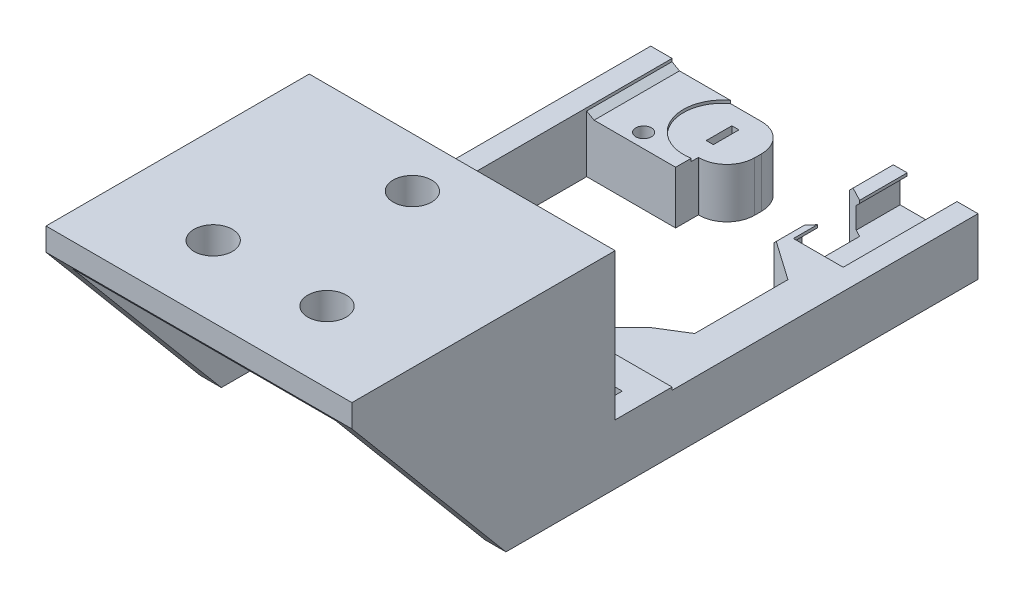
SolidWorks part; units mm, degrees
ref_plane "Front Plane" through (0, 0, 0) normal (0, 0, 1) x (1, 0, 0)
ref_plane "Top Plane" through (0, 0, 0) normal (0, 1, 0) x (1, 0, 0)
ref_plane "Right Plane" through (0, 0, 0) normal (1, 0, 0) x (0, 0, -1)
sketch "Sketch1" plane through (0, 0, 0) normal (0, 1, 0) x (1, 0, 0)
  line L0 (0, 0) -> (0, 59.6401) construction
  line L1 (-18.5, -19.2885) -> (-21.5, -19.2885)
  line L2 (18.5, 17.7115) -> (21.5, 17.7115)
  line L3 (18.5, 17.7115) -> (18.5, 65.7115)
  line L4 (18.5, 65.7115) -> (21.5, 65.7115)
  line L5 (21.5, 17.7115) -> (21.5, 65.7115)
  line L6 (18.5, 17.7115) -> (21.5, 17.7115)
  line L7 (18.5, 17.7115) -> (18.5, -19.2885)
  line L8 (18.5, -19.2885) -> (21.5, -19.2885)
  line L9 (21.5, 17.7115) -> (21.5, -19.2885)
  line L10 (-21.5, 17.7115) -> (-21.5, -19.2885)
  line L11 (-18.5, 17.7115) -> (-21.5, 17.7115)
  line L12 (-18.5, 17.7115) -> (-18.5, -19.2885)
  line L13 (-18.5, 65.7115) -> (-21.5, 65.7115)
  line L14 (-21.5, 17.7115) -> (-21.5, 65.7115)
  line L15 (-18.5, 17.7115) -> (-21.5, 17.7115)
  line L16 (-18.5, 17.7115) -> (-18.5, 65.7115)
  dimension "18" = 18.5
  dimension "D2" = 3
  dimension "D3" = 37
  dimension "D4" = 48
extrude "Boss-Extrude1" add sketch "Sketch1" against normal blind 8 contours L12 L11 L10 L1 | L11 L16 L13 L14 | L9 L2 L7 L8 | L2 L5 L4 L3 region at (-20, 0, 0.7885) region at (-20, 0, -41.7115) region at (20, 0, -41.7115) region at (20, 0, 0.7885)
sketch "Sketch2" plane through (21.5, 0, 0) normal (1, 0, 0) x (0, 0, -1)
  line L0 (-19.2885, -4) -> (65.7115, -4) construction
  line L1 (-19.2885, -8) -> (-19.2885, 0) construction
  line L2 (65.7115, -8) -> (65.7115, 0) construction
  line L3 (65.7115, -8) -> (-19.2885, -8) construction
  line L4 (17.7115, 0) -> (17.7115, -8) construction
  line L5 (65.7115, 0) -> (-19.2885, 0) construction
  circle A0 centre (11.7115, -4) radius 1.5
  circle A2 centre (-8.2885, -4) radius 1.5
  circle A3 centre (1.7115, -4) radius 1.5 [skipped]
  dimension "D2" = 3
  dimension "D1" = 4
  dimension "D3" = 37
  dimension "D4" = 6
  dimension "D5" = 3
extrude "Cut-Extrude1" [suppressed] cut sketch "Sketch2" against normal through all both and the other way through all
chamfer "Chamfer1" [suppressed] distance 1 angle 48
chamfer "Chamfer2" [suppressed] distance 1 angle 48
sketch "Sketch4" plane through (0, -8, 0) normal (0, -1, 0) x (1, 0, 0)
  line L0 (-21.5, -65.7115) -> (-21.5, 19.2885) construction
  line L1 (-2, -65.7115) -> (-21.5, -65.7115)
  line L2 (-2, -65.7115) -> (-2, -56.9115)
  line L3 (-2, -56.9115) -> (-21.5, -56.9115)
  line L4 (-21.5, -65.7115) -> (-21.5, -56.9115)
  line L10 (-18.5, -65.7115) -> (-18.5, 19.2885) construction
  line L13 (-18.5, -65.7115) -> (-21.5, -65.7115) construction
  dimension "D1" = 8.8
  dimension "D2" = 16.5
extrude "Boss-Extrude3" add sketch "Sketch4" against normal blind 6.6
sketch "Sketch3" plane through (0, -8, 0) normal (0, -1, 0) x (1, 0, 0)
  line L0 (-21.5, -65.7115) -> (-21.5, 19.2885) construction
  line L1 (-21.5, -57.7115) -> (-6, -57.7115)
  line L2 (-21.5, -57.7115) -> (-21.5, -53.7115)
  line L3 (-21.5, -53.7115) -> (-6, -53.7115)
  line L4 (-6, -57.7115) -> (-6, -53.7115)
  line L6 (0, 0) -> (0, -31.4212) construction
  line L13 (-2, -65.7115) -> (-21.5, -65.7115) construction
  line L14 (-21.5, -41.7115) -> (-3.8096, -41.7115) construction
  line L15 (-21.5, -29.7115) -> (-6, -29.7115)
  line L16 (-6, -25.7115) -> (-6, -29.7115)
  line L17 (-21.5, -25.7115) -> (-6, -25.7115)
  line L18 (-21.5, -25.7115) -> (-21.5, -29.7115)
  line L19 (-18.5, -56.9115) -> (-18.5, 19.2885) construction
  circle A0 centre (-12.5, -55.7115) radius 1.04
  circle A2 centre (-12.5, -27.7115) radius 1.04
  dimension "D4" = 2
  dimension "D5" = 2.08
  dimension "D1" = 14
  dimension "D2" = 10
  dimension "D3" = 4
  dimension "D6" = 6
  dimension "D7" = 15.5
extrude "Servo Holder" add sketch "Sketch3" along normal blind 0.4 and the other way offset from surface 1 other way up to plane "Top Plane"
sketch "Sketch5" plane through (0, 0, 0) normal (0, 1, 0) x (1, 0, 0)
  line L0 (-2, 61.3115) -> (-21.5, 61.3115) construction
  line L1 (-2, 65.7115) -> (-2, 56.9115) construction
  line L2 (-21.5, 65.7115) -> (-21.5, -19.2885) construction
  line L4 (-6.5, 63.1115) -> (-7.5, 63.1115)
  line L5 (-6.5, 63.1115) -> (-6.5, 59.5115)
  line L6 (-6.5, 59.5115) -> (-7.5, 59.5115)
  line L7 (-7.5, 63.1115) -> (-7.5, 59.5115)
  line L8 (-6.5, 63.1115) -> (-7.5, 59.5115) construction
  line L9 (-6.5, 59.5115) -> (-7.5, 63.1115) construction
  circle A0 centre (-12.5, 55.7115) radius 1.04 construction
  point P6 (-7, 61.3115)
  dimension "D3" = 5.5
  dimension "D1" = 1
  dimension "D2" = 3.6
extrude "Cut-Extrude2" cut sketch "Sketch5" against normal through all
sketch "Sketch6" plane through (0, -1.4, 0) normal (0, 1, 0) x (1, 0, 0)
  line L0 (-6.5, 61.3115) -> (-7.5, 61.3115) construction
  line L1 (-6.5, 59.5115) -> (-6.5, 63.1115) construction
  line L2 (-7.5, 63.1115) -> (-7.5, 59.5115) construction
  circle A0 centre (-7, 61.3115) radius 5.25
  dimension "D1" = 10.5
extrude "Brass" [suppressed] add sketch "Sketch6" along normal blind 2.6
fillet "Fillet1" [suppressed] radius 2.6
sketch "Sketch11" plane through (0, -8, 0) normal (0, -1, 0) x (1, 0, 0)
  line L0 (21.5, -65.7115) -> (21.5, 19.2885) construction
  line L1 (-21.5, -25.7115) -> (21.5, -25.7115)
  line L2 (-21.5, -25.7115) -> (-21.5, -21.7115)
  line L3 (-21.5, -21.7115) -> (21.5, -21.7115)
  line L4 (21.5, -25.7115) -> (21.5, -21.7115)
  dimension "D1" = 4
extrude "Boss-Extrude9" add sketch "Sketch11" against normal blind 8 and the other way up to surface (0.4 mm away) other way up to face at (-13.75, -8.4, -55.7115)
sketch "Sketch14" plane through (0, -8, 0) normal (0, -1, 0) x (1, 0, 0)
  line L1 (18.5, -25.7115) -> (30.7236, -25.7115)
  line L2 (18.5, -25.7115) -> (18.5, -70.6911)
  line L3 (18.5, -70.6911) -> (30.7236, -70.6911)
  line L4 (30.7236, -25.7115) -> (30.7236, -70.6911)
extrude "Cut-Extrude5" cut sketch "Sketch14" against normal blind 10
fillet "Fillet2" radius 3.9 2 edges at (-2, -4.7, -65.7115) (-2, -4.7, -56.9115)
sketch "Sketch13" plane through (0, -8.4, 0) normal (0, -1, 0) x (-1, 0, 0)
  circle A0 centre (12.5, 55.7115) radius 1.1
  circle A1 centre (12.5, 27.7115) radius 1.1
  dimension "D1" = 2.2
extrude "Cut-Extrude4" cut sketch "Sketch13" against normal through all both and the other way through all
sketch "Sketch17" plane through (0, 0, -25.7115) normal (0, 0, -1) x (-1, 0, 0)
  line L0 (-21.5, -8.4) -> (6, -8.4) construction
  line L1 (-8.6, -8.4) -> (-21.5, -8.4)
  line L2 (-8.6, -8.4) -> (-8.6, -0.4)
  line L3 (-8.6, -0.4) -> (-21.5, -0.4)
  line L4 (-21.5, -8.4) -> (-21.5, -0.4)
  line L5 (-21.5, -8.4) -> (-21.5, 0) construction
  dimension "D1" = 12.9
  dimension "D2" = 8
extrude "Boss-Extrude11" add sketch "Sketch17" along normal blind 27
sketch "Sketch16" plane through (0, 0, -52.7115) normal (0, 0, -1) x (-1, 0, 0)
  line L0 (-18.55, -2) -> (-18.55, -0.4)
  line L1 (-10.55, -4.8) -> (-19.75, -4.8)
  line L2 (-10.55, -4.8) -> (-10.55, -2)
  line L3 (-10.55, -2) -> (-19.75, -2)
  line L4 (-19.75, -4.8) -> (-19.75, -2)
  line L5 (-18.55, -0.4) -> (-21.5, -0.4)
  line L6 (-21.5, -0.4) -> (-21.5, -8.4)
  line L7 (-21.5, -8.4) -> (-8.6, -8.4)
  line L8 (-15.05, -4.3136) -> (-15.05, -1.3136) construction
  line L9 (-8.6, -8.4) -> (6, -8.4) construction
  line L10 (-8.6, -0.4) -> (-8.6, -8.4)
  line L11 (-11.55, -2) -> (-11.55, -0.4)
  line L12 (-11.55, -0.4) -> (-8.6, -0.4)
  line L13 (-21.5, -0.4) -> (-21.5, 0) construction
  line M30 (-8.6, -8.4) -> (-8.6, -0.4)
  line M31 (-8.6, -0.4) -> (-21.5, -0.4)
  line M32 (-21.5, -0.4) -> (-21.5, -8.4)
  line M33 (-21.5, -8.4) -> (-8.6, -8.4)
  dimension "D1" = 2.8
  dimension "D2" = 9.2
  dimension "D3" = 1.6
  dimension "D4" = 1.75
  dimension "D5" = 3.6
  dimension "D6" = 3.5
  dimension "D7" = 1.95
extrude "Boss-Extrude12" add sketch "Sketch16" along normal offset from surface (16 mm away) 3 contours L11 L3 L2 L1 L4 L0 M31 M32 M33 M30 region at (15.0111, -5.33, -52.7115) up to face at (-15.3, -3.1333, -65.7115) offset beyond the face yes
sketch "Sketch18" plane through (0, -8, 0) normal (0, -1, 0) x (1, 0, 0)
  line L0 (18.5, 19.2885) -> (21.5, 19.2885) construction
  line L1 (-21.5, -65.7115) -> (-5.9, -65.7115)
  line L2 (-21.5, -65.7115) -> (-21.5, -52.3785)
  line L5 (-21.5, -57.7115) -> (-18.5, -57.7115)
  line L6 (-21.5, -57.7115) -> (-21.5, 19.2885)
  line L7 (-21.5, 19.2885) -> (-18.5, 19.2885)
  line L8 (-18.5, -57.7115) -> (-18.5, 19.2885)
  line L9 (21.5, 19.2885) -> (18.5, 19.2885)
  line L10 (21.5, 19.2885) -> (21.5, -21.7115)
  line L11 (21.5, -21.7115) -> (18.5, -21.7115)
  line L12 (18.5, 19.2885) -> (18.5, -21.7115)
  line L13 (-18.5, 19.2885) -> (-21.5, 19.2885) construction
  line L14 (21.5, -21.7115) -> (21.5, 19.2885) construction
  line L15 (-18.5, -53.7115) -> (-18.5, -29.7115) construction
  line L16 (-2, -61.8115) -> (-2, -60.8115) construction
  arc A0 (-5.9, -56.9115) -> (-2, -60.8115) centre (-5.9, -60.8115) cw
  arc A1 (-5.9, -65.7115) -> (-2, -61.8115) centre (-5.9, -61.8115) ccw
  arc A5 (-2, -60.8115) -> (-5.9, -56.9115) centre (-5.9, -60.8115) ccw construction
  arc A6 (-5.9, -65.7115) -> (-2, -61.8115) centre (-5.9, -61.8115) ccw construction
  line M7 (-6.5, -63.1115) -> (-7.5, -63.1115)
  line M8 (-7.5, -63.1115) -> (-7.5, -59.5115)
  line M9 (-7.5, -59.5115) -> (-6.5, -59.5115)
  line M10 (-6.5, -59.5115) -> (-6.5, -63.1115)
  line M11 (-21.5, -65.7115) -> (-5.9, -65.7115)
  line M13 (-2, -61.8115) -> (-2, -60.8115)
  line M15 (-5.9, -56.9115) -> (-6, -56.9115)
  line M16 (-6, -56.9115) -> (-6, -57.7115)
  line M17 (-6, -57.7115) -> (-21.5, -57.7115)
  line M18 (-21.5, -57.7115) -> (-21.5, -65.7115)
extrude "Boss-Extrude13" add sketch "Sketch18" along normal up to surface (0.4 mm away) contours A1 A0 M11 M13 M15 M16 M17 M18 M10 M7 M8 M9 | L8 L7 L6 | L9 L12 L11 L10 | L6 L5 L8 L7 region at (-12.0872, -8, -61.6443) region at (-20, -8, -19.2115) region at (20, -8, -1.2115) up to face at (-12.5, -8.4, -26.6115)
chamfer "Chamfer14" distance 1.2 angle 45 2 edges at (18.55, -2, -60.7115) (11.55, -2, -60.7115)
sketch "Sketch20" plane through (0, -0.4, 0) normal (0, 1, 0) x (1, 0, 0)
  line L0 (11.55, 62.0219) -> (2.5155, 66.7653)
  line L1 (11.55, 68.7115) -> (11.55, 52.7115) construction
  line L2 (2.5155, 66.7653) -> (1.9978, 58.6591)
  line L3 (1.9978, 58.6591) -> (1.9978, 45.1224)
  line L4 (1.9978, 45.1224) -> (11.55, 56.0872)
  line L5 (11.55, 56.0872) -> (11.55, 62.0219)
  line L6 (8.6, 25.7115) -> (21.5, 25.7115) construction
  line L7 (9.7, 25.7115) -> (1.9978, 25.7115)
  line L8 (9.7, 25.7115) -> (9.7, 53.9636)
  line L9 (9.7, 53.9636) -> (1.9978, 53.9636)
  line L10 (1.9978, 25.7115) -> (1.9978, 53.9636)
  line L11 (21.5, 68.7115) -> (21.5, 25.7115) construction
  line L12 (16.1748, 47.3223) -> (4.9747, 55.1624)
  line L13 (4.9747, 55.1624) -> (4.9747, 27.2638)
  line L14 (4.9747, 27.2638) -> (16.1748, 34.2118)
  line L15 (16.1748, 34.2118) -> (16.1748, 47.3223)
  line M6 (8.6, 25.7115) -> (21.5, 25.7115)
  line M11 (11.55, 52.7115) -> (11.55, 68.7115)
  line M13 (8.6, 68.7115) -> (8.6, 25.7115)
  dimension "D1" = 11.8
extrude "Cut-Extrude6" cut sketch "Sketch20" against normal through all both and the other way through all contours L13 L12 L9 L0 L2 L3 M13 | L12 L9 M13 | L12 L4 L9 M13 | L12 L8 L4 | L14 L8 L12 L4 M13 | L14 L15 L12 L8 | L13 L14 L4 M13 | L9 L13 L4 L12 M13 | L12 L13 L9 | L9 L4 L0 M11 M13 | L4 L12 M13 | L14 L8 M13 M6 region at (9.9584, -0.4, -58.6946) region at (5.2143, -0.4, -59.6186) region at (7.9616, -0.4, -53.5183) region at (8.9667, -0.4, -53.5427) region at (9.3205, -0.4, -52.8242) region at (6.2284, -0.4, -51.906) region at (5.5455, -0.4, -54.3632) region at (12.6721, -0.4, -40.9066) region at (9.1441, -0.4, -41.0471) region at (6.8133, -0.4, -39.527) region at (9.1651, -0.4, -27.7874)
chamfer "Chamfer19" [suppressed] distance 0.7 angle 33
ref_plane "Plane1" through (0, 20.6, 0) normal (0, 1, 0) x (1, 0, 0)
sketch "Sketch22" plane through (0, 20.6, 0) normal (0, 1, 0) x (1, 0, 0)
  line L0 (0, 17.7115) -> (0, -19.2885) construction
  line L1 (-21.5, -19.2885) -> (21.5, -19.2885)
  line L2 (-21.5, -19.2885) -> (-21.5, 17.7115)
  line L3 (-21.5, 17.7115) -> (21.5, 17.7115)
  line L4 (21.5, -19.2885) -> (21.5, 17.7115)
  line L5 (-18.5, 21.7115) -> (-18.5, -19.2885) construction
  line L6 (18.5, 21.7115) -> (18.5, -19.2885) construction
  line L7 (-21.5, -19.2885) -> (-21.5, 65.7115) construction
  line L9 (-18.5, -19.2885) -> (-21.5, -19.2885) construction
  circle A0 centre (0, 10.7115) radius 2.7
  circle A2 centre (8, -9.2885) radius 2.7
  circle A3 centre (-8, -9.2885) radius 2.7
  dimension "D3" = 7
  dimension "D4" = 10
  dimension "D6" = 5.4
  dimension "D1" = 37
  dimension "D5" = 8
extrude "Mount Top" add sketch "Sketch22" against normal blind 4 separate body
sketch "Sketch23" plane through (-21.5, 0, 0) normal (-1, 0, 0) x (0, 0, 1)
  line L0 (19.2885, 16.6) -> (19.2885, 20.6) construction
  line L1 (19.2885, 20.6) -> (-17.7115, 20.6)
  line L2 (19.2885, 20.6) -> (19.2885, -8.4)
  line L3 (19.2885, -8.4) -> (-17.7115, -8.4)
  line L4 (-17.7115, 20.6) -> (-17.7115, -8.4)
  line L5 (-65.7115, -8.4) -> (19.2885, -8.4) construction
  line L6 (-17.7115, 20.6) -> (19.2885, 20.6) construction
extrude "Mount Side1" add sketch "Sketch23" against normal up to surface (3 mm away) up to face at (-18.5, -4.2, -1.2115)
sketch "Sketch24" plane through (21.5, 0, 0) normal (1, 0, 0) x (0, 0, -1)
  line L0 (-19.2885, -8.4) -> (68.7115, -8.4) construction
  line L1 (-19.2885, 20.6) -> (17.7115, 20.6)
  line L2 (-19.2885, 20.6) -> (-19.2885, -8.4)
  line L3 (-19.2885, -8.4) -> (17.7115, -8.4)
  line L4 (17.7115, 20.6) -> (17.7115, -8.4)
extrude "Mount Side2" add sketch "Sketch24" against normal up to surface (3 mm away) up to face at (18.5, -4.2, -1.2115)
chamfer "Chamfer20" distance 25.8 angle 40 2 edges at (20, -8.4, 19.2885) (-20, -8.4, 19.2885) first distance on face at (0, 5.1, 19.2885)
sketch "Sketch29" plane through (0, -1.4, 0) normal (0, 1, 0) x (1, 0, 0)
  line L0 (-18.5, 57.7115) -> (-6, 57.7115) construction
  line L1 (-18.5, 65.7115) -> (-9.6141, 65.7115)
  line L2 (-18.5, 65.7115) -> (-18.5, 57.7115)
  line L3 (-18.5, 57.7115) -> (-9.6141, 57.7115)
  line L4 (-9.6141, 65.7115) -> (-9.6141, 57.7115)
extrude "Boss-Extrude20" add sketch "Sketch29" along normal up to surface (0.4 mm away) up to face at (-12.5, -1, -54.6115)
sketch "Sketch25" [suppressed] plane through (0, 0, -17.7115) normal (0, 0, -1) x (-1, 0, 0)
  line L0 (21.5, 20.6) -> (21.5, 0) construction
  line L1 (-21.5, -0.4) -> (21.5, -0.4)
  line L2 (-21.5, -0.4) -> (-21.5, 0.5976)
  line L3 (-21.5, 0.5976) -> (21.5, 0.5976)
  line L4 (21.5, -0.4) -> (21.5, 0.5976)
  line L6 (18.5, -1) -> (0, -1)
  line L7 (18.5, -1) -> (18.5, -1.6016)
  line L8 (18.5, -1.6016) -> (0, -1.6016)
  line L9 (0, -1) -> (0, -1.6016)
extrude "Cut-Extrude7" [suppressed] cut sketch "Sketch25" along normal through all
chamfer "Chamfer22" [suppressed] distance 2 angle 45
chamfer "Chamfer23" distance 1 angle 45 1 edges at (9.7, -0.4, -52.9091)
chamfer "Chamfer24" distance 1 angle 45 3 edges at (8.6, -0.4, -66.1411) (-6, -4.7, -29.7115) (9.7, -4.4, -30.1952) first distance on face at (8.6, -4.4, -66.1411) first distance on face at (-6, -4.7, -27.7115) first distance on face at (9.7, -4.4, -27.9534)
sketch "Sketch26" plane through (0, -1.4, 0) normal (0, 1, 0) x (1, 0, 0)
  line L0 (-7.5, 63.1115) -> (-6.5, 63.1115) construction
  line L1 (-7.5, 59.5115) -> (-7.5, 63.1115) construction
  circle A0 centre (-7, 61.3115) radius 5.5
  dimension "D1" = 11
  dimension "D2" = 1.8
  dimension "D3" = 0.5
extrude "Cut-Extrude8" cut sketch "Sketch26" along normal blind 10
chamfer "Chamfer25" distance 0.6 angle 60 1 edges at (-18.5, -1, -59.7115) first distance on face at (-18.5, -2.6, -43.7115)
